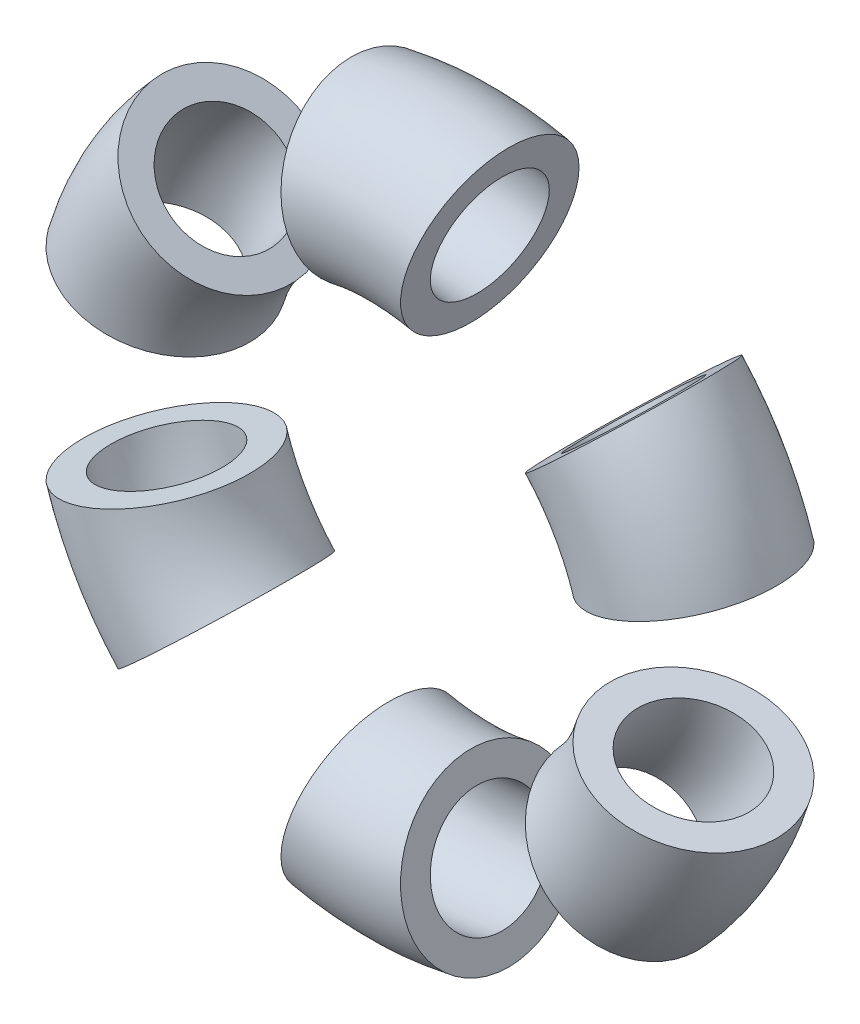
SolidWorks part; units mm, degrees
ref_plane "Ebene vorne" through (0, 0, 0) normal (0, 0, 1) x (1, 0, 0)
ref_plane "Ebene oben" through (0, 0, 0) normal (0, 1, 0) x (1, 0, 0)
ref_plane "Ebene rechts" through (0, 0, 0) normal (1, 0, 0) x (0, 0, -1)
ref_axis "Achse1" through (0, 0, 3.3) along (0, 0, -1)
sketch "Skizze2" plane through (0, 0, 0) normal (1, 0, 0) x (0, 0, -1)
  line L0 (0, 30.3347) -> (0, -31.6126) construction
  line L1 (-37.7282, 0) -> (33.6511, 0) construction
  circle A0 centre (0, 9.5) radius 3
  circle A1 centre (0, 9.5) radius 2
  dimension "D2" = 6
  dimension "D3" = 4
  dimension "D1" = 9.5
revolve "Rotation1" add sketch "Skizze2" angle 25 mid plane about L1
pattern_circular "Kreismuster1" count 6 over 360 about axis through (0, 0, 3.3) along (0, 0, -1) of "Rotation1"
